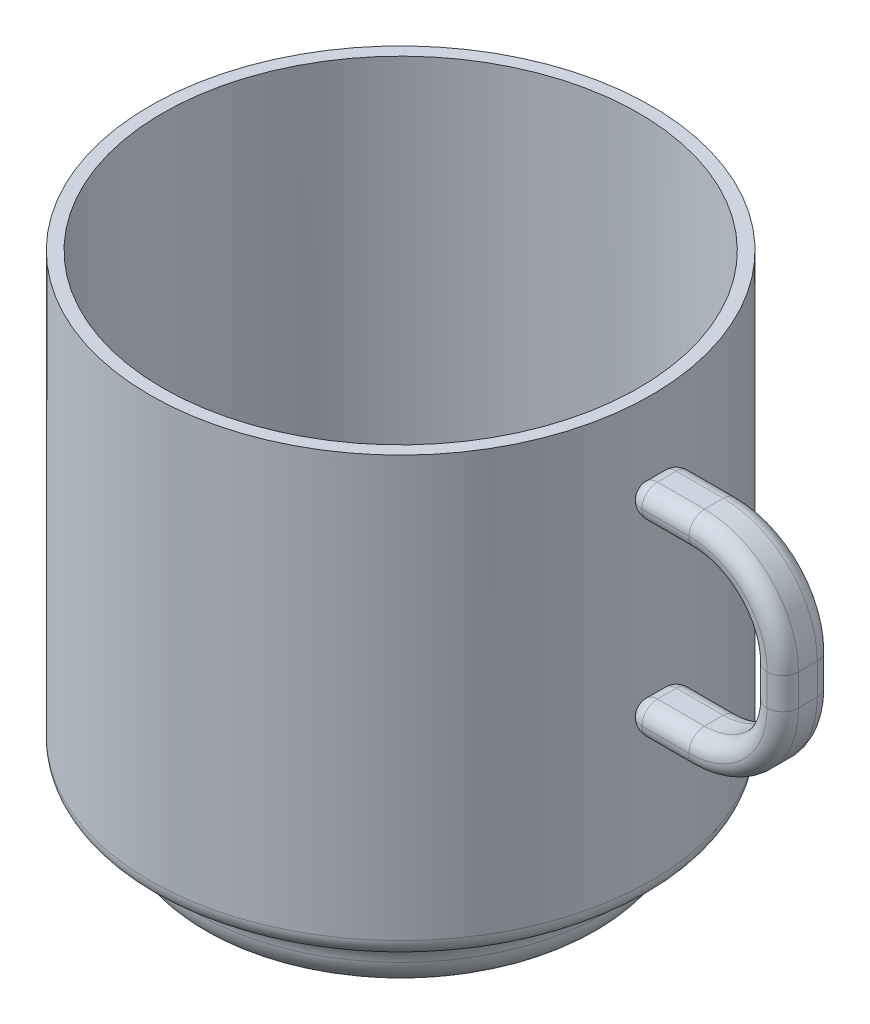
SolidWorks part; units mm, degrees
ref_plane "정면" through (0, 0, 0) normal (0, 0, 1) x (1, 0, 0)
ref_plane "윗면" through (0, 0, 0) normal (0, 1, 0) x (1, 0, 0)
ref_plane "우측면" through (0, 0, 0) normal (1, 0, 0) x (0, 0, -1)
sketch "스케치1" plane through (0, 0, 0) normal (0, 0, 1) x (1, 0, 0)
  line L0 (-1.7658, 50.3929) -> (-1.7658, -152.0787) construction
  line L1 (-41.7658, 5.1395) -> (-1.7658, 5.1395)
  line L2 (-41.7658, 5.1395) -> (-41.7658, -64.8605)
  line L3 (-41.7658, -64.8605) -> (-40.2658, -64.8605)
  line L4 (-34.2658, -70.8605) -> (-34.2658, -71.8605)
  line L5 (-31.2658, -74.8605) -> (-1.7658, -74.8605)
  line L6 (-40.2658, -64.8605) -> (-34.2658, -64.8605)
  line L7 (-34.2658, -64.8605) -> (-34.2658, -70.8605)
  line L8 (-31.2658, -74.8605) -> (-34.2658, -74.8605)
  line L9 (-34.2658, -74.8605) -> (-34.2658, -71.8605)
  line L10 (-1.7658, 5.1395) -> (-1.7658, -74.8605)
revolve "회전1" add sketch "스케치1" angle 360 about L10
fillet "필렛1" radius 5 1 edges at (-1.7658, -74.8605, 32.5)
fillet "필렛2" radius 6 1 edges at (-1.7658, -64.8605, 32.5)
fillet "필렛4" radius 3 1 edges at (-1.7658, -64.8605, 40)
shell "쉘3" thickness 2 removed face at (-1.7658, 5.1395, 40)
sketch "스케치2" plane through (0, 0, 0) normal (0, 0, 1) x (1, 0, 0)
  line L0 (58.2342, -19.8605) -> (58.2342, -24.8605)
  line L5 (48.2342, -4.8605) -> (38.2342, -4.8605)
  line L6 (63.2342, -19.8605) -> (63.2342, -24.8605)
  line L7 (48.2342, -39.8605) -> (38.2342, -39.8605)
  line L8 (38.2342, -4.8605) -> (38.2342, -9.8605)
  line L9 (48.2342, -34.8605) -> (43.2342, -34.8605)
  line L11 (48.2342, -9.8605) -> (43.2342, -9.8605)
  line L12 (43.2342, -9.8605) -> (38.2342, -9.8605)
  line L13 (43.2342, -34.8605) -> (38.2342, -34.8605)
  line L14 (38.2342, -34.8605) -> (38.2342, -39.8605)
  line L15 (43.2342, -9.8605) -> (43.2342, -34.8605) construction
  line L16 (38.2342, -4.8605) -> (38.2342, -39.8605) construction
  arc A0 (48.2342, -4.8605) -> (63.2342, -19.8605) centre (48.2342, -19.8605) cw
  arc A1 (63.2342, -24.8605) -> (48.2342, -39.8605) centre (48.2342, -24.8605) cw
  arc A2 (48.2342, -9.8605) -> (58.2342, -19.8605) centre (48.2342, -19.8605) cw
  arc A3 (58.2342, -24.8605) -> (48.2342, -34.8605) centre (48.2342, -24.8605) cw
  dimension "D1" = 25
  dimension "D2" = 35
  dimension "D4" = 10
  dimension "D3" = 5
extrude "보스-돌출1" add sketch "스케치2" along normal blind 4 and the other way blind 4 separate body
ref_plane "평면3" through (38.2342, -4.8605, 4) normal (0, -1, 0) x (-1, 0, 0)
fillet "필렛6" radius 2.5 15 edges at (43.2342, -39.8605, -4) (58.8408, -35.4671, -4) (63.2342, -22.3605, -4) (43.2342, -4.8605, -4) (43.2342, -39.8605, 4) (58.8408, -35.4671, 4) (63.2342, -22.3605, 4) (43.2342, -4.8605, 4) (43.2342, -9.8605, 4) (43.2342, -34.8605, 4) (55.3052, -31.9316, 4) (58.2342, -22.3605, 4) (58.8408, -9.2539, -4) (58.8408, -9.2539, 4) (55.3052, -12.7895, 4)
fillet "필렛7" radius 2.5 15 edges at (38.2342, -9.8605, -1.25) (38.2342, -9.1283, 3.2678) (38.2342, -5.5928, 3.2678) (38.2342, -4.8605, 0) (38.2342, -5.5928, -3.2678) (38.2342, -34.8605, -1.25) (38.2342, -35.5928, 3.2678) (38.2342, -39.1283, 3.2678) (38.2342, -39.8605, 0) (38.2342, -39.1283, -3.2678) (43.2342, -9.8605, -4) (55.3052, -12.7895, -4) (58.2342, -22.3605, -4) (55.3052, -31.9316, -4) (43.2342, -34.8605, -4)
